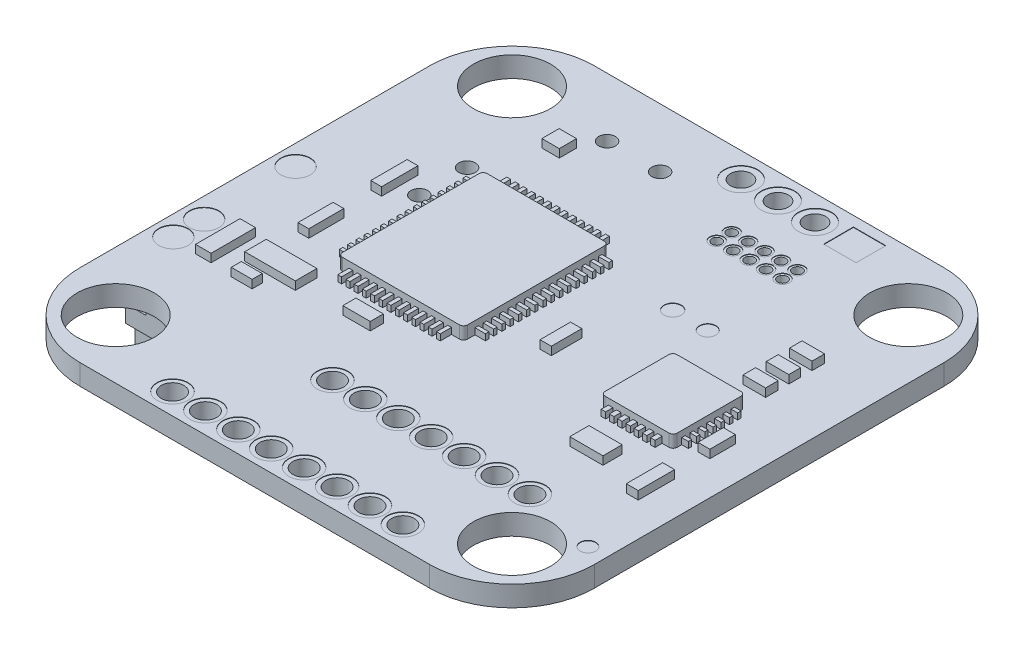
SolidWorks part; units mm, degrees
ref_plane "Front Plane" through (0, 0, 0) normal (0, 0, 1) x (1, 0, 0)
ref_plane "Top Plane" through (0, 0, 0) normal (0, 1, 0) x (1, 0, 0)
ref_plane "Right Plane" through (0, 0, 0) normal (1, 0, 0) x (0, 0, -1)
sketch "Sketch1" plane through (0, 0, 0) normal (0, 1, 0) x (1, 0, 0)
  line L1 (15.875, 15.875) -> (-15.875, 15.875)
  line L2 (15.875, 15.875) -> (15.875, -15.875)
  line L3 (15.875, -15.875) -> (-15.875, -15.875)
  line L4 (-15.875, 15.875) -> (-15.875, -15.875)
  line L5 (15.875, 15.875) -> (-15.875, -15.875) construction
  line L6 (15.875, -15.875) -> (-15.875, 15.875) construction
  point P0 (0, 0)
  dimension "D1" = 31.75
  dimension "D2" = 31.75
extrude "Boss-Extrude1" add sketch "Sketch1" along normal blind 1.27
fillet "Fillet1" radius 5.08 4 edges at (15.875, 0.635, -15.875) (-15.875, 0.635, -15.875) (-15.875, 0.635, 15.875) (15.875, 0.635, 15.875)
sketch "Sketch2" plane through (0, 1.27, 0) normal (0, 1, 0) x (1, 0, 0)
  line L0 (15.875, 0) -> (-15.875, 0) construction
  line L1 (15.875, -10.795) -> (15.875, 10.795) construction
  line L2 (-15.875, 10.795) -> (-15.875, -10.795) construction
  line L3 (0, 0) -> (0, 15.875) construction
  line L4 (10.795, 15.875) -> (-10.795, 15.875) construction
  line L5 (14.3871, 14.3871) -> (0, 0) construction
  arc A0 (15.875, 10.795) -> (10.795, 15.875) centre (10.795, 10.795) ccw construction
  circle A1 centre (12.2354, 12.2354) radius 2.3813
  circle A2 centre (-12.2354, 12.2354) radius 2.3813
  circle A3 centre (-12.2354, -12.2354) radius 2.3813
  circle A4 centre (12.2354, -12.2354) radius 2.3813
  circle A5 centre (-6.3651, 12.2354) radius 0.5132
  circle A6 centre (-3.0883, 12.2354) radius 0.5132
  circle A7 centre (-9.2733, 6.4988) radius 0.5132
  circle A8 centre (-9.2733, 3.5497) radius 0.5132
  dimension "D1" = 4.7625
extrude "Cut-Extrude1" cut sketch "Sketch2" against normal blind 2540
sketch "Sketch3" plane through (0, 1.27, 0) normal (0, 1, 0) x (1, 0, 0)
  line L1 (-0.0888, 6.0397) -> (-7.8229, 6.0397)
  line L2 (-0.0888, 6.0397) -> (-0.0888, -2.9028)
  line L3 (-0.0888, -2.9028) -> (-7.8229, -2.9028)
  line L4 (-7.8229, 6.0397) -> (-7.8229, -2.9028)
  line L5 (-0.0888, 6.0397) -> (-7.8229, -2.9028) construction
  line L6 (-0.0888, -2.9028) -> (-7.8229, 6.0397) construction
  line L7 (12.169, 2.2203) -> (7.7135, 2.2203)
  line L8 (12.169, 2.2203) -> (12.169, -2.2203)
  line L9 (12.169, -2.2203) -> (7.7135, -2.2203)
  line L10 (7.7135, 2.2203) -> (7.7135, -2.2203)
  line L11 (12.169, 2.2203) -> (7.7135, -2.2203) construction
  line L12 (12.169, -2.2203) -> (7.7135, 2.2203) construction
  point P0 (-3.9559, 1.5684)
  point P5 (9.9412, 0)
extrude "Boss-Extrude2" add sketch "Sketch3" along normal blind 0.762
sketch "Sketch4" plane through (0, 1.27, 0) normal (0, 1, 0) x (1, 0, 0)
  line L1 (-10.3847, 4.5784) -> (-11.0506, 4.5784)
  line L2 (-10.3847, 4.5784) -> (-10.3847, 2.3308)
  line L3 (-10.3847, 2.3308) -> (-11.0506, 2.3308)
  line L4 (-11.0506, 4.5784) -> (-11.0506, 2.3308)
  line L5 (-10.3847, 0) -> (-11.0506, 0)
  line L6 (-10.3847, 0) -> (-10.3847, -2.1643)
  line L7 (-10.3847, -2.1643) -> (-11.0506, -2.1643)
  line L8 (-11.0506, 0) -> (-11.0506, -2.1643)
  line L9 (-12.0912, -3.746) -> (-13.0485, -3.746)
  line L10 (-12.0912, -3.746) -> (-12.0912, -6.493)
  line L11 (-12.0912, -6.493) -> (-13.0485, -6.493)
  line L12 (-13.0485, -3.746) -> (-13.0485, -6.493)
  line L13 (-11.1339, -4.0373) -> (-8.0122, -4.0373)
  line L14 (-11.1339, -4.0373) -> (-11.1339, -5.3692)
  line L15 (-11.1339, -5.3692) -> (-8.0122, -5.3692)
  line L16 (-8.0122, -4.0373) -> (-8.0122, -5.3692)
  line L17 (-9.4274, -5.9936) -> (-10.7177, -5.9936)
  line L18 (-9.4274, -5.9936) -> (-9.4274, -6.6179)
  line L19 (-9.4274, -6.6179) -> (-10.7177, -6.6179)
  line L20 (-10.7177, -5.9936) -> (-10.7177, -6.6179)
  line L21 (-5.2236, -4.4119) -> (-3.531, -4.4119)
  line L22 (-5.2236, -4.4119) -> (-5.2236, -5.223)
  line L23 (-5.2236, -5.223) -> (-3.531, -5.223)
  line L24 (-3.531, -4.4119) -> (-3.531, -5.223)
  line L25 (3.3834, 0.9282) -> (2.687, 0.9282)
  line L26 (3.3834, 0.9282) -> (3.3834, -0.9559)
  line L27 (3.3834, -0.9559) -> (2.687, -0.9559)
  line L28 (2.687, 0.9282) -> (2.687, -0.9559)
  line L29 (-6.9386, 10.9225) -> (-8.0122, 10.9225)
  line L30 (-6.9386, 10.9225) -> (-6.9386, 9.8575)
  line L31 (-6.9386, 9.8575) -> (-8.0122, 9.8575)
  line L32 (-8.0122, 10.9225) -> (-8.0122, 9.8575)
  line L33 (12.2307, 7.0722) -> (10.8381, 7.0722)
  line L34 (12.2307, 7.0722) -> (12.2307, 6.294)
  line L35 (12.2307, 6.294) -> (10.8381, 6.294)
  line L36 (10.8381, 7.0722) -> (10.8381, 6.294)
  line L37 (12.2307, 5.5977) -> (10.8381, 5.5977)
  line L38 (12.2307, 5.5977) -> (12.2307, 4.8604)
  line L39 (12.2307, 4.8604) -> (10.8381, 4.8604)
  line L40 (10.8381, 5.5977) -> (10.8381, 4.8604)
  line L41 (12.2307, 4.205) -> (10.8381, 4.205)
  line L42 (12.2307, 4.205) -> (12.2307, 3.4268)
  line L43 (12.2307, 3.4268) -> (10.8381, 3.4268)
  line L44 (10.8381, 4.205) -> (10.8381, 3.4268)
  line L45 (10.8381, -4.0373) -> (8.7901, -4.0373)
  line L46 (10.8381, -4.0373) -> (10.8381, -5.223)
  line L47 (10.8381, -5.223) -> (8.7901, -5.223)
  line L48 (8.7901, -4.0373) -> (8.7901, -5.223)
  line L49 (13.7872, 0) -> (13.0499, 0)
  line L50 (13.7872, 0) -> (13.7872, -1.5703)
  line L51 (13.7872, -1.5703) -> (13.0499, -1.5703)
  line L52 (13.0499, 0) -> (13.0499, -1.5703)
  line L53 (13.7872, -3.746) -> (13.0499, -3.746)
  line L54 (13.7872, -3.746) -> (13.7872, -5.9936)
  line L55 (13.7872, -5.9936) -> (13.0499, -5.9936)
  line L56 (13.0499, -3.746) -> (13.0499, -5.9936)
extrude "Boss-Extrude3" add sketch "Sketch4" along normal blind 0.508
sketch "Sketch5" plane through (0, 1.27, 0) normal (0, 1, 0) x (1, 0, 0)
  line L0 (-0.3573, 5.1281) -> (0.5564, 5.1281)
  line L1 (-0.3573, 5.6361) -> (0.5564, 5.6361)
  line L2 (-0.3573, 5.6361) -> (-0.3573, 5.4223)
  line L3 (-0.3573, 5.4223) -> (0.5564, 5.4223)
  line L4 (0.5564, 5.6361) -> (0.5564, 5.4223)
  line L5 (-7.5497, 5.6361) -> (-8.4633, 5.6361)
  line L6 (-7.5497, 5.6361) -> (-7.5497, 5.4223)
  line L7 (-7.5497, 5.4223) -> (-8.4633, 5.4223)
  line L8 (-8.4633, 5.6361) -> (-8.4633, 5.4223)
  line L9 (-0.3573, 5.1281) -> (-0.3573, 4.9143)
  line L10 (-0.3573, 4.9143) -> (0.5564, 4.9143)
  line L11 (0.5564, 5.1281) -> (0.5564, 4.9143)
  line L12 (-7.5497, 5.1281) -> (-8.4633, 5.1281)
  line L13 (-7.5497, 5.1281) -> (-7.5497, 4.9143)
  line L14 (-7.5497, 4.9143) -> (-8.4633, 4.9143)
  line L15 (-8.4633, 5.1281) -> (-8.4633, 4.9143)
  line L16 (-0.3573, 4.6201) -> (0.5564, 4.6201)
  line L17 (-0.3573, 4.6201) -> (-0.3573, 4.4063)
  line L18 (-0.3573, 4.4063) -> (0.5564, 4.4063)
  line L19 (0.5564, 4.6201) -> (0.5564, 4.4063)
  line L20 (-7.5497, 4.6201) -> (-8.4633, 4.6201)
  line L21 (-7.5497, 4.6201) -> (-7.5497, 4.4063)
  line L22 (-7.5497, 4.4063) -> (-8.4633, 4.4063)
  line L23 (-8.4633, 4.6201) -> (-8.4633, 4.4063)
  line L24 (-0.3573, 4.1121) -> (0.5564, 4.1121)
  line L25 (-0.3573, 4.1121) -> (-0.3573, 3.8983)
  line L26 (-0.3573, 3.8983) -> (0.5564, 3.8983)
  line L27 (0.5564, 4.1121) -> (0.5564, 3.8983)
  line L28 (-7.5497, 4.1121) -> (-8.4633, 4.1121)
  line L29 (-7.5497, 4.1121) -> (-7.5497, 3.8983)
  line L30 (-7.5497, 3.8983) -> (-8.4633, 3.8983)
  line L31 (-8.4633, 4.1121) -> (-8.4633, 3.8983)
  line L32 (-0.3573, 3.6042) -> (0.5564, 3.6042)
  line L33 (-0.3573, 3.6042) -> (-0.3573, 3.3903)
  line L34 (-0.3573, 3.3903) -> (0.5564, 3.3903)
  line L35 (0.5564, 3.6042) -> (0.5564, 3.3903)
  line L36 (-7.5497, 3.6042) -> (-8.4633, 3.6042)
  line L37 (-7.5497, 3.6042) -> (-7.5497, 3.3903)
  line L38 (-7.5497, 3.3903) -> (-8.4633, 3.3903)
  line L39 (-8.4633, 3.6042) -> (-8.4633, 3.3903)
  line L40 (-0.3573, 3.0962) -> (0.5564, 3.0962)
  line L41 (-0.3573, 3.0962) -> (-0.3573, 2.8823)
  line L42 (-0.3573, 2.8823) -> (0.5564, 2.8823)
  line L43 (0.5564, 3.0962) -> (0.5564, 2.8823)
  line L44 (-7.5497, 3.0962) -> (-8.4633, 3.0962)
  line L45 (-7.5497, 3.0962) -> (-7.5497, 2.8823)
  line L46 (-7.5497, 2.8823) -> (-8.4633, 2.8823)
  line L47 (-8.4633, 3.0962) -> (-8.4633, 2.8823)
  line L48 (-0.3573, 2.5882) -> (0.5564, 2.5882)
  line L49 (-0.3573, 2.5882) -> (-0.3573, 2.3743)
  line L50 (-0.3573, 2.3743) -> (0.5564, 2.3743)
  line L51 (0.5564, 2.5882) -> (0.5564, 2.3743)
  line L52 (-7.5497, 2.5882) -> (-8.4633, 2.5882)
  line L53 (-7.5497, 2.5882) -> (-7.5497, 2.3743)
  line L54 (-7.5497, 2.3743) -> (-8.4633, 2.3743)
  line L55 (-8.4633, 2.5882) -> (-8.4633, 2.3743)
  line L56 (-0.3573, 2.0802) -> (0.5564, 2.0802)
  line L57 (-0.3573, 2.0802) -> (-0.3573, 1.8663)
  line L58 (-0.3573, 1.8663) -> (0.5564, 1.8663)
  line L59 (0.5564, 2.0802) -> (0.5564, 1.8663)
  line L60 (-7.5497, 2.0802) -> (-8.4633, 2.0802)
  line L61 (-7.5497, 2.0802) -> (-7.5497, 1.8663)
  line L62 (-7.5497, 1.8663) -> (-8.4633, 1.8663)
  line L63 (-8.4633, 2.0802) -> (-8.4633, 1.8663)
  line L64 (-0.3573, 1.5722) -> (0.5564, 1.5722)
  line L65 (-0.3573, 1.5722) -> (-0.3573, 1.3584)
  line L66 (-0.3573, 1.3584) -> (0.5564, 1.3584)
  line L67 (0.5564, 1.5722) -> (0.5564, 1.3584)
  line L68 (-7.5497, 1.5722) -> (-8.4633, 1.5722)
  line L69 (-7.5497, 1.5722) -> (-7.5497, 1.3584)
  line L70 (-7.5497, 1.3584) -> (-8.4633, 1.3584)
  line L71 (-8.4633, 1.5722) -> (-8.4633, 1.3584)
  line L72 (-0.3573, 1.0642) -> (0.5564, 1.0642)
  line L73 (-0.3573, 1.0642) -> (-0.3573, 0.8504)
  line L74 (-0.3573, 0.8504) -> (0.5564, 0.8504)
  line L75 (0.5564, 1.0642) -> (0.5564, 0.8504)
  line L76 (-7.5497, 1.0642) -> (-8.4633, 1.0642)
  line L77 (-7.5497, 1.0642) -> (-7.5497, 0.8504)
  line L78 (-7.5497, 0.8504) -> (-8.4633, 0.8504)
  line L79 (-8.4633, 1.0642) -> (-8.4633, 0.8504)
  line L80 (-0.3573, 0.5562) -> (0.5564, 0.5562)
  line L81 (-0.3573, 0.5562) -> (-0.3573, 0.3424)
  line L82 (-0.3573, 0.3424) -> (0.5564, 0.3424)
  line L83 (0.5564, 0.5562) -> (0.5564, 0.3424)
  line L84 (-7.5497, 0.5562) -> (-8.4633, 0.5562)
  line L85 (-7.5497, 0.5562) -> (-7.5497, 0.3424)
  line L86 (-7.5497, 0.3424) -> (-8.4633, 0.3424)
  line L87 (-8.4633, 0.5562) -> (-8.4633, 0.3424)
  line L88 (-0.3573, 0.0482) -> (0.5564, 0.0482)
  line L89 (-0.3573, 0.0482) -> (-0.3573, -0.1656)
  line L90 (-0.3573, -0.1656) -> (0.5564, -0.1656)
  line L91 (0.5564, 0.0482) -> (0.5564, -0.1656)
  line L92 (-7.5497, 0.0482) -> (-8.4633, 0.0482)
  line L93 (-7.5497, 0.0482) -> (-7.5497, -0.1656)
  line L94 (-7.5497, -0.1656) -> (-8.4633, -0.1656)
  line L95 (-8.4633, 0.0482) -> (-8.4633, -0.1656)
  line L96 (-0.3573, -0.4598) -> (0.5564, -0.4598)
  line L97 (-0.3573, -0.4598) -> (-0.3573, -0.6736)
  line L98 (-0.3573, -0.6736) -> (0.5564, -0.6736)
  line L99 (0.5564, -0.4598) -> (0.5564, -0.6736)
  line L100 (-7.5497, -0.4598) -> (-8.4633, -0.4598)
  line L101 (-7.5497, -0.4598) -> (-7.5497, -0.6736)
  line L102 (-7.5497, -0.6736) -> (-8.4633, -0.6736)
  line L103 (-8.4633, -0.4598) -> (-8.4633, -0.6736)
  line L104 (-0.3573, -0.9678) -> (0.5564, -0.9678)
  line L105 (-0.3573, -0.9678) -> (-0.3573, -1.1816)
  line L106 (-0.3573, -1.1816) -> (0.5564, -1.1816)
  line L107 (0.5564, -0.9678) -> (0.5564, -1.1816)
  line L108 (-7.5497, -0.9678) -> (-8.4633, -0.9678)
  line L109 (-7.5497, -0.9678) -> (-7.5497, -1.1816)
  line L110 (-7.5497, -1.1816) -> (-8.4633, -1.1816)
  line L111 (-8.4633, -0.9678) -> (-8.4633, -1.1816)
  line L112 (-0.3573, -1.4758) -> (0.5564, -1.4758)
  line L113 (-0.3573, -1.4758) -> (-0.3573, -1.6896)
  line L114 (-0.3573, -1.6896) -> (0.5564, -1.6896)
  line L115 (0.5564, -1.4758) -> (0.5564, -1.6896)
  line L116 (-7.5497, -1.4758) -> (-8.4633, -1.4758)
  line L117 (-7.5497, -1.4758) -> (-7.5497, -1.6896)
  line L118 (-7.5497, -1.6896) -> (-8.4633, -1.6896)
  line L119 (-8.4633, -1.4758) -> (-8.4633, -1.6896)
  line L120 (-0.3573, -1.9838) -> (0.5564, -1.9838)
  line L121 (-0.3573, -1.9838) -> (-0.3573, -2.1976)
  line L122 (-0.3573, -2.1976) -> (0.5564, -2.1976)
  line L123 (0.5564, -1.9838) -> (0.5564, -2.1976)
  line L124 (-7.5497, -1.9838) -> (-8.4633, -1.9838)
  line L125 (-7.5497, -1.9838) -> (-7.5497, -2.1976)
  line L126 (-7.5497, -2.1976) -> (-8.4633, -2.1976)
  line L127 (-8.4633, -1.9838) -> (-8.4633, -2.1976)
  line L128 (-6.6529, 5.7722) -> (-6.4196, 5.7722)
  line L129 (-7.1609, 5.7722) -> (-6.9276, 5.7722)
  line L130 (-7.1609, 5.7722) -> (-7.1609, 6.8413)
  line L131 (-7.1609, 6.8413) -> (-6.9276, 6.8413)
  line L132 (-6.9276, 5.7722) -> (-6.9276, 6.8413)
  line L133 (-7.1609, -2.5088) -> (-6.9276, -2.5088)
  line L134 (-7.1609, -2.5088) -> (-7.1609, -3.5974)
  line L135 (-7.1609, -3.5974) -> (-6.9276, -3.5974)
  line L136 (-6.9276, -2.5088) -> (-6.9276, -3.5974)
  line L137 (-6.6529, 5.7722) -> (-6.6529, 6.8413)
  line L138 (-6.6529, 6.8413) -> (-6.4196, 6.8413)
  line L139 (-6.4196, 5.7722) -> (-6.4196, 6.8413)
  line L140 (-6.6529, -2.5088) -> (-6.4196, -2.5088)
  line L141 (-6.6529, -2.5088) -> (-6.6529, -3.5974)
  line L142 (-6.6529, -3.5974) -> (-6.4196, -3.5974)
  line L143 (-6.4196, -2.5088) -> (-6.4196, -3.5974)
  line L144 (-6.1449, 5.7722) -> (-5.9116, 5.7722)
  line L145 (-6.1449, 5.7722) -> (-6.1449, 6.8413)
  line L146 (-6.1449, 6.8413) -> (-5.9116, 6.8413)
  line L147 (-5.9116, 5.7722) -> (-5.9116, 6.8413)
  line L148 (-6.1449, -2.5088) -> (-5.9116, -2.5088)
  line L149 (-6.1449, -2.5088) -> (-6.1449, -3.5974)
  line L150 (-6.1449, -3.5974) -> (-5.9116, -3.5974)
  line L151 (-5.9116, -2.5088) -> (-5.9116, -3.5974)
  line L152 (-5.6369, 5.7722) -> (-5.4036, 5.7722)
  line L153 (-5.6369, 5.7722) -> (-5.6369, 6.8413)
  line L154 (-5.6369, 6.8413) -> (-5.4036, 6.8413)
  line L155 (-5.4036, 5.7722) -> (-5.4036, 6.8413)
  line L156 (-5.6369, -2.5088) -> (-5.4036, -2.5088)
  line L157 (-5.6369, -2.5088) -> (-5.6369, -3.5974)
  line L158 (-5.6369, -3.5974) -> (-5.4036, -3.5974)
  line L159 (-5.4036, -2.5088) -> (-5.4036, -3.5974)
  line L160 (-5.1289, 5.7722) -> (-4.8956, 5.7722)
  line L161 (-5.1289, 5.7722) -> (-5.1289, 6.8413)
  line L162 (-5.1289, 6.8413) -> (-4.8956, 6.8413)
  line L163 (-4.8956, 5.7722) -> (-4.8956, 6.8413)
  line L164 (-5.1289, -2.5088) -> (-4.8956, -2.5088)
  line L165 (-5.1289, -2.5088) -> (-5.1289, -3.5974)
  line L166 (-5.1289, -3.5974) -> (-4.8956, -3.5974)
  line L167 (-4.8956, -2.5088) -> (-4.8956, -3.5974)
  line L168 (-4.6209, 5.7722) -> (-4.3876, 5.7722)
  line L169 (-4.6209, 5.7722) -> (-4.6209, 6.8413)
  line L170 (-4.6209, 6.8413) -> (-4.3876, 6.8413)
  line L171 (-4.3876, 5.7722) -> (-4.3876, 6.8413)
  line L172 (-4.6209, -2.5088) -> (-4.3876, -2.5088)
  line L173 (-4.6209, -2.5088) -> (-4.6209, -3.5974)
  line L174 (-4.6209, -3.5974) -> (-4.3876, -3.5974)
  line L175 (-4.3876, -2.5088) -> (-4.3876, -3.5974)
  line L176 (-4.1129, 5.7722) -> (-3.8796, 5.7722)
  line L177 (-4.1129, 5.7722) -> (-4.1129, 6.8413)
  line L178 (-4.1129, 6.8413) -> (-3.8796, 6.8413)
  line L179 (-3.8796, 5.7722) -> (-3.8796, 6.8413)
  line L180 (-4.1129, -2.5088) -> (-3.8796, -2.5088)
  line L181 (-4.1129, -2.5088) -> (-4.1129, -3.5974)
  line L182 (-4.1129, -3.5974) -> (-3.8796, -3.5974)
  line L183 (-3.8796, -2.5088) -> (-3.8796, -3.5974)
  line L184 (-3.6049, 5.7722) -> (-3.3716, 5.7722)
  line L185 (-3.6049, 5.7722) -> (-3.6049, 6.8413)
  line L186 (-3.6049, 6.8413) -> (-3.3716, 6.8413)
  line L187 (-3.3716, 5.7722) -> (-3.3716, 6.8413)
  line L188 (-3.6049, -2.5088) -> (-3.3716, -2.5088)
  line L189 (-3.6049, -2.5088) -> (-3.6049, -3.5974)
  line L190 (-3.6049, -3.5974) -> (-3.3716, -3.5974)
  line L191 (-3.3716, -2.5088) -> (-3.3716, -3.5974)
  line L192 (-3.0969, 5.7722) -> (-2.8636, 5.7722)
  line L193 (-3.0969, 5.7722) -> (-3.0969, 6.8413)
  line L194 (-3.0969, 6.8413) -> (-2.8636, 6.8413)
  line L195 (-2.8636, 5.7722) -> (-2.8636, 6.8413)
  line L196 (-3.0969, -2.5088) -> (-2.8636, -2.5088)
  line L197 (-3.0969, -2.5088) -> (-3.0969, -3.5974)
  line L198 (-3.0969, -3.5974) -> (-2.8636, -3.5974)
  line L199 (-2.8636, -2.5088) -> (-2.8636, -3.5974)
  line L200 (-2.5889, 5.7722) -> (-2.3556, 5.7722)
  line L201 (-2.5889, 5.7722) -> (-2.5889, 6.8413)
  line L202 (-2.5889, 6.8413) -> (-2.3556, 6.8413)
  line L203 (-2.3556, 5.7722) -> (-2.3556, 6.8413)
  line L204 (-2.5889, -2.5088) -> (-2.3556, -2.5088)
  line L205 (-2.5889, -2.5088) -> (-2.5889, -3.5974)
  line L206 (-2.5889, -3.5974) -> (-2.3556, -3.5974)
  line L207 (-2.3556, -2.5088) -> (-2.3556, -3.5974)
  line L208 (-2.0809, 5.7722) -> (-1.8476, 5.7722)
  line L209 (-2.0809, 5.7722) -> (-2.0809, 6.8413)
  line L210 (-2.0809, 6.8413) -> (-1.8476, 6.8413)
  line L211 (-1.8476, 5.7722) -> (-1.8476, 6.8413)
  line L212 (-2.0809, -2.5088) -> (-1.8476, -2.5088)
  line L213 (-2.0809, -2.5088) -> (-2.0809, -3.5974)
  line L214 (-2.0809, -3.5974) -> (-1.8476, -3.5974)
  line L215 (-1.8476, -2.5088) -> (-1.8476, -3.5974)
  line L216 (-1.5729, 5.7722) -> (-1.3396, 5.7722)
  line L217 (-1.5729, 5.7722) -> (-1.5729, 6.8413)
  line L218 (-1.5729, 6.8413) -> (-1.3396, 6.8413)
  line L219 (-1.3396, 5.7722) -> (-1.3396, 6.8413)
  line L220 (-1.5729, -2.5088) -> (-1.3396, -2.5088)
  line L221 (-1.5729, -2.5088) -> (-1.5729, -3.5974)
  line L222 (-1.5729, -3.5974) -> (-1.3396, -3.5974)
  line L223 (-1.3396, -2.5088) -> (-1.3396, -3.5974)
  line L224 (-1.0649, 5.7722) -> (-0.8316, 5.7722)
  line L225 (-1.0649, 5.7722) -> (-1.0649, 6.8413)
  line L226 (-1.0649, 6.8413) -> (-0.8316, 6.8413)
  line L227 (-0.8316, 5.7722) -> (-0.8316, 6.8413)
  line L228 (-1.0649, -2.5088) -> (-0.8316, -2.5088)
  line L229 (-1.0649, -2.5088) -> (-1.0649, -3.5974)
  line L230 (-1.0649, -3.5974) -> (-0.8316, -3.5974)
  line L231 (-0.8316, -2.5088) -> (-0.8316, -3.5974)
  line L232 (7.3458, -1.1816) -> (8.1656, -1.1816)
  line L233 (7.3458, -1.6896) -> (8.1656, -1.6896)
  line L234 (7.3458, -1.6896) -> (7.3458, -1.4758)
  line L235 (7.3458, -1.4758) -> (8.1656, -1.4758)
  line L236 (8.1656, -1.6896) -> (8.1656, -1.4758)
  line L237 (11.8217, -1.6896) -> (12.5758, -1.6896)
  line L238 (11.8217, -1.6896) -> (11.8217, -1.4794)
  line L239 (11.8217, -1.4794) -> (12.5758, -1.4794)
  line L240 (12.5758, -1.6896) -> (12.5758, -1.4794)
  line L241 (7.3458, -1.1816) -> (7.3458, -0.9678)
  line L242 (7.3458, -0.9678) -> (8.1656, -0.9678)
  line L243 (8.1656, -1.1816) -> (8.1656, -0.9678)
  line L244 (11.8217, -1.1816) -> (12.5758, -1.1816)
  line L245 (11.8217, -1.1816) -> (11.8217, -0.9714)
  line L246 (11.8217, -0.9714) -> (12.5758, -0.9714)
  line L247 (12.5758, -1.1816) -> (12.5758, -0.9714)
  line L248 (7.3458, -0.6736) -> (8.1656, -0.6736)
  line L249 (7.3458, -0.6736) -> (7.3458, -0.4598)
  line L250 (7.3458, -0.4598) -> (8.1656, -0.4598)
  line L251 (8.1656, -0.6736) -> (8.1656, -0.4598)
  line L252 (11.8217, -0.6736) -> (12.5758, -0.6736)
  line L253 (11.8217, -0.6736) -> (11.8217, -0.4634)
  line L254 (11.8217, -0.4634) -> (12.5758, -0.4634)
  line L255 (12.5758, -0.6736) -> (12.5758, -0.4634)
  line L256 (7.3458, -0.1656) -> (8.1656, -0.1656)
  line L257 (7.3458, -0.1656) -> (7.3458, 0.0482)
  line L258 (7.3458, 0.0482) -> (8.1656, 0.0482)
  line L259 (8.1656, -0.1656) -> (8.1656, 0.0482)
  line L260 (11.8217, -0.1656) -> (12.5758, -0.1656)
  line L261 (11.8217, -0.1656) -> (11.8217, 0.0446)
  line L262 (11.8217, 0.0446) -> (12.5758, 0.0446)
  line L263 (12.5758, -0.1656) -> (12.5758, 0.0446)
  line L264 (7.3458, 0.3424) -> (8.1656, 0.3424)
  line L265 (7.3458, 0.3424) -> (7.3458, 0.5562)
  line L266 (7.3458, 0.5562) -> (8.1656, 0.5562)
  line L267 (8.1656, 0.3424) -> (8.1656, 0.5562)
  line L268 (11.8217, 0.3424) -> (12.5758, 0.3424)
  line L269 (11.8217, 0.3424) -> (11.8217, 0.5526)
  line L270 (11.8217, 0.5526) -> (12.5758, 0.5526)
  line L271 (12.5758, 0.3424) -> (12.5758, 0.5526)
  line L272 (7.3458, 0.8504) -> (8.1656, 0.8504)
  line L273 (7.3458, 0.8504) -> (7.3458, 1.0642)
  line L274 (7.3458, 1.0642) -> (8.1656, 1.0642)
  line L275 (8.1656, 0.8504) -> (8.1656, 1.0642)
  line L276 (11.8217, 0.8504) -> (12.5758, 0.8504)
  line L277 (11.8217, 0.8504) -> (11.8217, 1.0606)
  line L278 (11.8217, 1.0606) -> (12.5758, 1.0606)
  line L279 (12.5758, 0.8504) -> (12.5758, 1.0606)
  line L280 (7.3458, 1.3584) -> (8.1656, 1.3584)
  line L281 (7.3458, 1.3584) -> (7.3458, 1.5722)
  line L282 (7.3458, 1.5722) -> (8.1656, 1.5722)
  line L283 (8.1656, 1.3584) -> (8.1656, 1.5722)
  line L284 (11.8217, 1.3584) -> (12.5758, 1.3584)
  line L285 (11.8217, 1.3584) -> (11.8217, 1.5686)
  line L286 (11.8217, 1.5686) -> (12.5758, 1.5686)
  line L287 (12.5758, 1.3584) -> (12.5758, 1.5686)
  line L288 (8.6736, -1.9838) -> (8.9523, -1.9838)
  line L289 (8.1656, 1.8663) -> (8.4443, 1.8663)
  line L290 (8.1656, 1.8663) -> (8.1656, 2.5882)
  line L291 (8.1656, 2.5882) -> (8.4443, 2.5882)
  line L292 (8.4443, 1.8663) -> (8.4443, 2.5882)
  line L293 (8.1656, -1.9838) -> (8.4443, -1.9838)
  line L294 (8.1656, -1.9838) -> (8.1656, -2.6599)
  line L295 (8.1656, -2.6599) -> (8.4443, -2.6599)
  line L296 (8.4443, -1.9838) -> (8.4443, -2.6599)
  line L297 (8.6736, -1.9838) -> (8.6736, -2.6599)
  line L298 (8.6736, -2.6599) -> (8.9523, -2.6599)
  line L299 (8.9523, -1.9838) -> (8.9523, -2.6599)
  line L300 (8.6736, 1.8663) -> (8.9523, 1.8663)
  line L301 (8.6736, 1.8663) -> (8.6736, 2.5882)
  line L302 (8.6736, 2.5882) -> (8.9523, 2.5882)
  line L303 (8.9523, 1.8663) -> (8.9523, 2.5882)
  line L304 (9.1816, -1.9838) -> (9.4603, -1.9838)
  line L305 (9.1816, -1.9838) -> (9.1816, -2.6599)
  line L306 (9.1816, -2.6599) -> (9.4603, -2.6599)
  line L307 (9.4603, -1.9838) -> (9.4603, -2.6599)
  line L308 (9.1816, 1.8663) -> (9.4603, 1.8663)
  line L309 (9.1816, 1.8663) -> (9.1816, 2.5882)
  line L310 (9.1816, 2.5882) -> (9.4603, 2.5882)
  line L311 (9.4603, 1.8663) -> (9.4603, 2.5882)
  line L312 (9.6896, -1.9838) -> (9.9683, -1.9838)
  line L313 (9.6896, -1.9838) -> (9.6896, -2.6599)
  line L314 (9.6896, -2.6599) -> (9.9683, -2.6599)
  line L315 (9.9683, -1.9838) -> (9.9683, -2.6599)
  line L316 (9.6896, 1.8663) -> (9.9683, 1.8663)
  line L317 (9.6896, 1.8663) -> (9.6896, 2.5882)
  line L318 (9.6896, 2.5882) -> (9.9683, 2.5882)
  line L319 (9.9683, 1.8663) -> (9.9683, 2.5882)
  line L320 (10.1976, -1.9838) -> (10.4763, -1.9838)
  line L321 (10.1976, -1.9838) -> (10.1976, -2.6599)
  line L322 (10.1976, -2.6599) -> (10.4763, -2.6599)
  line L323 (10.4763, -1.9838) -> (10.4763, -2.6599)
  line L324 (10.1976, 1.8663) -> (10.4763, 1.8663)
  line L325 (10.1976, 1.8663) -> (10.1976, 2.5882)
  line L326 (10.1976, 2.5882) -> (10.4763, 2.5882)
  line L327 (10.4763, 1.8663) -> (10.4763, 2.5882)
  line L328 (10.7056, -1.9838) -> (10.9843, -1.9838)
  line L329 (10.7056, -1.9838) -> (10.7056, -2.6599)
  line L330 (10.7056, -2.6599) -> (10.9843, -2.6599)
  line L331 (10.9843, -1.9838) -> (10.9843, -2.6599)
  line L332 (10.7056, 1.8663) -> (10.9843, 1.8663)
  line L333 (10.7056, 1.8663) -> (10.7056, 2.5882)
  line L334 (10.7056, 2.5882) -> (10.9843, 2.5882)
  line L335 (10.9843, 1.8663) -> (10.9843, 2.5882)
  line L336 (11.2136, -1.9838) -> (11.4923, -1.9838)
  line L337 (11.2136, -1.9838) -> (11.2136, -2.6599)
  line L338 (11.2136, -2.6599) -> (11.4923, -2.6599)
  line L339 (11.4923, -1.9838) -> (11.4923, -2.6599)
  line L340 (11.2136, 1.8663) -> (11.4923, 1.8663)
  line L341 (11.2136, 1.8663) -> (11.2136, 2.5882)
  line L342 (11.2136, 2.5882) -> (11.4923, 2.5882)
  line L343 (11.4923, 1.8663) -> (11.4923, 2.5882)
  dimension "D1" = 16
  dimension "D2" = 13
  dimension "D3" = 7
  dimension "D4" = 7
extrude "Boss-Extrude4" add sketch "Sketch5" along normal blind 0.381
sketch "Sketch6" plane through (0, 1.27, 0) normal (0, 1, 0) x (1, 0, 0)
  line L1 (7.8249, 13.4231) -> (5.8271, 13.4231)
  line L2 (7.8249, 13.4231) -> (7.8249, 15.2545)
  line L3 (7.8249, 15.2545) -> (5.8271, 15.2545)
  line L4 (5.8271, 13.4231) -> (5.8271, 15.2545)
  circle A0 centre (4.3703, 14.3388) radius 1.028
  circle A1 centre (2.0843, 14.3388) radius 1.028
  circle A2 centre (-0.2017, 14.3388) radius 1.028
  circle A3 centre (6.4098, 11.2171) radius 0.4263
  circle A4 centre (6.4098, 10.2934) radius 0.4263
  circle A5 centre (5.3938, 11.2171) radius 0.4263
  circle A6 centre (5.3938, 10.2934) radius 0.4263
  circle A7 centre (4.3778, 11.2171) radius 0.4263
  circle A8 centre (4.3778, 10.2934) radius 0.4263
  circle A9 centre (3.3618, 11.2171) radius 0.4263
  circle A10 centre (3.3618, 10.2934) radius 0.4263
  circle A11 centre (2.3458, 11.2171) radius 0.4263
  circle A12 centre (2.3458, 10.2934) radius 0.4263
  circle A13 centre (-14.6347, 1.2695) radius 0.9051
  circle A14 centre (-14.6347, -4.3754) radius 0.9051
  circle A15 centre (-14.6347, -6.2731) radius 0.9051
  circle A16 centre (6.8557, 5.2299) radius 0.5046
  circle A17 centre (4.6914, 5.2299) radius 0.5345
  circle A18 centre (14.7259, -10.0382) radius 0.4787
  circle A19 centre (10.1218, -9.0151) radius 0.9522
  circle A20 centre (8.0898, -9.0151) radius 0.9522
  circle A21 centre (6.0578, -9.0151) radius 0.9522
  circle A22 centre (4.0258, -9.0151) radius 0.9522
  circle A23 centre (1.9938, -9.0151) radius 0.9522
  circle A24 centre (-0.0382, -9.0151) radius 0.9522
  circle A25 centre (-2.0702, -9.0151) radius 0.9522
  circle A26 centre (7.8249, -14.5636) radius 0.9522
  circle A27 centre (5.7929, -14.5636) radius 0.9522
  circle A28 centre (3.7609, -14.5636) radius 0.9522
  circle A29 centre (1.7289, -14.5636) radius 0.9522
  circle A30 centre (-0.3031, -14.5636) radius 0.9522
  circle A31 centre (-2.3351, -14.5636) radius 0.9522
  circle A32 centre (-4.3671, -14.5636) radius 0.9522
  circle A33 centre (-6.3991, -14.5636) radius 0.9522
  dimension "D1" = 3
  dimension "D2" = 5
  dimension "D3" = 7
  dimension "D4" = 8
extrude "Cut-Extrude2" cut sketch "Sketch6" against normal blind 0.0254
fillet "Fillet2" radius 0.254 8 edges at (-0.0888, 1.651, 2.9028) (-7.8229, 1.651, 2.9028) (-7.8229, 1.651, -6.0397) (-0.0888, 1.651, -6.0397) (12.169, 1.651, 2.2203) (12.169, 1.651, -2.2203) (7.7135, 1.651, 2.2203) (7.7135, 1.651, -2.2203)
sketch "Sketch7" plane through (0, 0, 0) normal (0, -1, 0) x (1, 0, 0)
  line L1 (12.5906, 7.0757) -> (-2.1435, 7.0757)
  line L2 (12.5906, 7.0757) -> (12.5906, -8.7822)
  line L3 (12.5906, -8.7822) -> (-2.1435, -8.7822)
  line L4 (-2.1435, 7.0757) -> (-2.1435, -8.7822)
  line L5 (-10.8009, -1.4151) -> (-15.379, -1.4151)
  line L6 (-10.8009, -1.4151) -> (-10.8009, -8.7822)
  line L7 (-10.8009, -8.7822) -> (-15.379, -8.7822)
  line L8 (-15.379, -1.4151) -> (-15.379, -8.7822)
extrude "Boss-Extrude5" add sketch "Sketch7" along normal blind 1.905
sketch "Sketch8" plane through (12.5906, 0, 0) normal (1, 0, 0) x (0, 0, -1)
  line L1 (-6.6081, -0.2398) -> (8.2748, -0.2398)
  line L2 (-6.6081, -0.2398) -> (-6.6081, -1.6198)
  line L3 (-6.6081, -1.6198) -> (8.2748, -1.6198)
  line L4 (8.2748, -0.2398) -> (8.2748, -1.6198)
extrude "Cut-Extrude3" cut sketch "Sketch8" against normal blind 13.97
sketch "Sketch10" plane through (-15.379, 0, 0) normal (-1, 0, 0) x (0, 0, 1)
  line L1 (-1.6982, -1.5672) -> (-8.497, -1.5672)
  line L2 (-1.6982, -1.5672) -> (-1.6982, -0.2327)
  line L3 (-1.6982, -0.2327) -> (-8.497, -0.2327)
  line L4 (-8.497, -1.5672) -> (-8.497, -0.2327)
extrude "Cut-Extrude4" cut sketch "Sketch10" against normal blind 3.81
sketch "Sketch11" plane through (0, -1.905, 0) normal (0, -1, 0) x (1, 0, 0)
  line L0 (12.5906, 3.9734) -> (7.7579, 1.1034)
  line L1 (12.5906, -8.7822) -> (12.5906, 7.0757) construction
  line L2 (7.7579, 1.1034) -> (7.7579, -5.7178)
  line L3 (7.7579, -5.7178) -> (12.5906, -7.6037)
  line L4 (12.5906, -7.6037) -> (12.5906, 3.9734)
extrude "Cut-Extrude5" cut sketch "Sketch11" against normal blind 1.27
sketch "Sketch12" plane through (0, -0.2398, 0) normal (0, -1, 0) x (1, 0, 0)
  line L1 (6.4722, 0.5411) -> (3.4338, 0.5411)
  line L2 (6.4722, 0.5411) -> (6.4722, -3.2881)
  line L3 (6.4722, -3.2881) -> (3.4338, -3.2881)
  line L4 (3.4338, 0.5411) -> (3.4338, -3.2881)
  line L5 (6.4722, -3.8292) -> (3.4338, -3.8292)
  line L6 (6.4722, -3.8292) -> (6.4722, -7.8249)
  line L7 (6.4722, -7.8249) -> (3.4338, -7.8249)
  line L8 (3.4338, -3.8292) -> (3.4338, -7.8249)
extrude "Cut-Extrude6" cut sketch "Sketch12" against normal blind 1.27
sketch "Sketch13" plane through (0, -0.2398, 0) normal (0, -1, 0) x (1, 0, 0)
  line L0 (12.5906, -8.2748) -> (12.5906, 6.6081) construction
  line L1 (12.5906, 1.9979) -> (10.9258, 1.9979)
  line L2 (12.5906, 1.9979) -> (12.5906, -7.6584)
  line L3 (12.5906, -7.6584) -> (10.9258, -7.6584)
  line L4 (10.9258, 1.9979) -> (10.9258, -7.6584)
extrude "Cut-Extrude7" cut sketch "Sketch13" against normal up to surface (0.2398 mm away) up to face at (-12.2354, 0, -14.6166)
sketch "Sketch14" plane through (0, -1.905, 0) normal (0, -1, 0) x (1, 0, 0)
  line L0 (-10.8009, -8.7822) -> (-10.8009, -1.4151) construction
  line L1 (-10.8009, -2.7054) -> (-12.2161, -2.7054)
  line L2 (-10.8009, -2.7054) -> (-10.8009, -4.1622)
  line L3 (-10.8009, -4.1622) -> (-12.2161, -4.1622)
  line L4 (-12.2161, -2.7054) -> (-12.2161, -4.1622)
  line L6 (-10.8009, -6.2017) -> (-12.2161, -6.2017)
  line L7 (-10.8009, -6.2017) -> (-10.8009, -7.8249)
  line L8 (-10.8009, -7.8249) -> (-12.2161, -7.8249)
  line L9 (-12.2161, -6.2017) -> (-12.2161, -7.8249)
  line L10 (-13.3398, -2.2892) -> (-14.8799, -2.2892)
  line L11 (-13.3398, -2.2892) -> (-13.3398, -3.1216)
  line L12 (-13.3398, -3.1216) -> (-14.8799, -3.1216)
  line L13 (-14.8799, -2.2892) -> (-14.8799, -3.1216)
  line L14 (-13.3398, -7.1174) -> (-14.8799, -7.1174)
  line L15 (-13.3398, -7.1174) -> (-13.3398, -8.1163)
  line L16 (-13.3398, -8.1163) -> (-14.8799, -8.1163)
  line L17 (-14.8799, -7.1174) -> (-14.8799, -8.1163)
extrude "Cut-Extrude8" cut sketch "Sketch14" against normal blind 1.27
sketch "Sketch15" plane through (0, 0, 0) normal (0, -1, 0) x (-1, 0, 0)
  line L0 (9.3025, -1.7065) -> (9.3025, -0.9646)
  line L1 (15.4612, -8.4144) -> (9.3025, -8.4144)
  line L2 (15.4612, -8.4144) -> (15.4612, -0.9646)
  line L3 (15.4612, -0.9646) -> (9.3025, -0.9646)
  line L4 (9.3025, -8.4144) -> (9.3025, -7.7001)
  line L5 (9.3025, -7.7001) -> (10.8841, -7.7001)
  line L7 (9.3025, -1.7065) -> (10.8841, -1.7065)
  line L8 (10.8841, -7.7001) -> (10.8841, -1.7065)
extrude "Boss-Extrude6" add sketch "Sketch15" along normal blind 4.572
sketch "Sketch16" plane through (-15.4612, 0, 0) normal (-1, 0, 0) x (0, 0, 1)
  line L0 (5.235, -3.8269) -> (7.4617, -3.8269)
  line L1 (1.9941, -0.868) -> (7.4617, -0.868)
  line L2 (1.9941, -0.868) -> (1.9941, -3.8269)
  line L3 (1.9941, -3.8269) -> (4.1499, -3.8269)
  line L4 (7.4617, -0.868) -> (7.4617, -3.8269)
  line L6 (4.1499, -3.8269) -> (4.1499, -4.2647)
  line L7 (4.1499, -4.2647) -> (5.235, -4.2647)
  line L8 (5.235, -3.8269) -> (5.235, -4.2647)
  line L9 (2.9362, -2.6832) -> (3.6166, -2.6832)
  line L10 (2.9362, -2.6832) -> (2.9362, -3.1245)
  line L11 (2.9362, -3.1245) -> (3.6166, -3.1245)
  line L12 (3.6166, -2.6832) -> (3.6166, -3.1245)
  line L13 (5.8786, -2.6832) -> (6.5223, -2.6832)
  line L14 (5.8786, -2.6832) -> (5.8786, -3.1245)
  line L15 (5.8786, -3.1245) -> (6.5223, -3.1245)
  line L16 (6.5223, -2.6832) -> (6.5223, -3.1245)
  line L17 (0.9646, -4.572) -> (0.9646, 0) construction
  line L18 (0.9646, -2.6832) -> (1.5202, -2.6832)
  line L19 (0.9646, -2.6832) -> (0.9646, -3.1245)
  line L20 (0.9646, -3.1245) -> (1.5202, -3.1245)
  line L21 (1.5202, -2.6832) -> (1.5202, -3.1245)
  line L22 (8.4144, -4.572) -> (8.4144, 0) construction
  line L23 (8.4144, -3.1245) -> (7.8096, -3.1245)
  line L24 (8.4144, -3.1245) -> (8.4144, -2.6832)
  line L25 (8.4144, -2.6832) -> (7.8096, -2.6832)
  line L26 (7.8096, -3.1245) -> (7.8096, -2.6832)
extrude "Cut-Extrude9" cut sketch "Sketch16" against normal blind 4.572
sketch "Sketch17" plane through (-15.4612, 0, 0) normal (-1, 0, 0) x (0, 0, 1)
  line L0 (8.4144, -4.572) -> (8.4144, -3.1245) construction
  line L1 (0.9646, -3.1245) -> (1.5202, -3.1245)
  line L2 (0.9646, -3.1245) -> (0.9646, -3.8594)
  line L3 (0.9646, -3.8594) -> (1.5202, -3.8594)
  line L4 (1.5202, -3.1245) -> (1.5202, -3.8594)
  line L5 (7.8096, -3.1245) -> (8.4144, -3.1245)
  line L6 (7.8096, -3.1245) -> (7.8096, -3.8594)
  line L7 (7.8096, -3.8594) -> (8.4144, -3.8594)
  line L8 (8.4144, -3.1245) -> (8.4144, -3.8594)
extrude "Cut-Extrude10" cut sketch "Sketch17" against normal blind 3.048
sketch "Sketch18" plane through (-15.4612, 0, 0) normal (-1, 0, 0) x (0, 0, 1)
  line L0 (8.4144, -4.572) -> (0.9646, -4.572) construction
  line L1 (0.9646, -3.8594) -> (1.5202, -3.8594)
  line L2 (0.9646, -3.8594) -> (0.9646, -4.572)
  line L3 (0.9646, -4.572) -> (1.5202, -4.572)
  line L4 (1.5202, -3.8594) -> (1.5202, -4.572)
  line L5 (0.9646, -2.6832) -> (0.9646, 0) construction
  line L6 (7.8096, -3.8594) -> (8.4144, -3.8594)
  line L7 (7.8096, -3.8594) -> (7.8096, -4.572)
  line L8 (7.8096, -4.572) -> (8.4144, -4.572)
  line L9 (8.4144, -3.8594) -> (8.4144, -4.572)
  line L10 (0.9646, -1.6286) -> (1.5202, -1.6286)
  line L11 (0.9646, -1.6286) -> (0.9646, 0)
  line L12 (0.9646, 0) -> (1.5202, 0)
  line L13 (1.5202, -1.6286) -> (1.5202, 0)
  line L14 (8.4144, 0) -> (0.9646, 0) construction
  line L15 (8.4144, -2.6832) -> (8.4144, 0) construction
  line L16 (8.4144, -1.6286) -> (7.8096, -1.6286)
  line L17 (8.4144, -1.6286) -> (8.4144, 0)
  line L18 (8.4144, 0) -> (7.8096, 0)
  line L19 (7.8096, -1.6286) -> (7.8096, 0)
extrude "Cut-Extrude11" cut sketch "Sketch18" against normal blind 1.27
sketch "Sketch19" plane through (0, 0, 0) normal (0, -1, 0) x (-1, 0, 0)
  line L1 (7.7209, 13.4439) -> (1.5608, 13.4439)
  line L2 (7.7209, 13.4439) -> (7.7209, 10.6552)
  line L3 (7.7209, 10.6552) -> (1.5608, 10.6552)
  line L4 (1.5608, 13.4439) -> (1.5608, 10.6552)
extrude "Boss-Extrude7" add sketch "Sketch19" along normal blind 1.27
sketch "Sketch20" plane through (0, 0, 0) normal (0, -1, 0) x (-1, 0, 0)
  line L0 (10.8841, -1.7065) -> (10.8841, -7.7001) construction
  line L1 (8.0539, 6.6595) -> (5.9728, 6.6595)
  line L2 (8.0539, 6.6595) -> (8.0539, 5.4525)
  line L3 (8.0539, 5.4525) -> (5.9728, 5.4525)
  line L4 (5.9728, 6.6595) -> (5.9728, 5.4525)
  line L5 (6.5971, 3.3298) -> (3.7668, 3.3298)
  line L6 (6.5971, 3.3298) -> (6.5971, 1.6649)
  line L7 (6.5971, 1.6649) -> (3.7668, 1.6649)
  line L8 (3.7668, 3.3298) -> (3.7668, 1.6649)
  line L9 (4.8906, 7.9082) -> (4.2663, 7.9082)
  line L10 (4.8906, 7.9082) -> (4.8906, 6.056)
  line L11 (4.8906, 6.056) -> (4.2663, 6.056)
  line L12 (4.2663, 7.9082) -> (4.2663, 6.056)
  line L13 (3.7668, 7.9082) -> (3.1008, 7.9082)
  line L14 (3.7668, 7.9082) -> (3.7668, 6.056)
  line L15 (3.7668, 6.056) -> (3.1008, 6.056)
  line L16 (3.1008, 7.9082) -> (3.1008, 6.056)
  line L17 (4.2663, 9.6563) -> (3.1008, 9.6563)
  line L18 (4.2663, 9.6563) -> (4.2663, 8.8655)
  line L19 (4.2663, 8.8655) -> (3.1008, 8.8655)
  line L20 (3.1008, 9.6563) -> (3.1008, 8.8655)
  line L21 (10.1766, 0.4578) -> (9.053, 0.4578)
  line L22 (10.1766, 0.4578) -> (10.1766, -0.1953)
  line L23 (10.1766, -0.1953) -> (9.053, -0.1953)
  line L24 (9.053, 0.4578) -> (9.053, -0.1953)
  line L25 (10.8841, -3.4379) -> (8.0539, -3.4379)
  line L26 (10.8841, -3.4379) -> (10.8841, -4.2374)
  line L27 (10.8841, -4.2374) -> (8.0539, -4.2374)
  line L28 (8.0539, -3.4379) -> (8.0539, -4.2374)
  line L30 (10.8841, -5.1074) -> (8.0539, -5.1074)
  line L31 (10.8841, -5.1074) -> (10.8841, -5.8599)
  line L32 (10.8841, -5.8599) -> (8.0539, -5.8599)
  line L33 (8.0539, -5.1074) -> (8.0539, -5.8599)
  line L34 (5.5682, -0.5221) -> (4.8906, -0.5221)
  line L35 (5.5682, -0.5221) -> (5.5682, -1.9094)
  line L36 (5.5682, -1.9094) -> (4.8906, -1.9094)
  line L37 (4.8906, -0.5221) -> (4.8906, -1.9094)
  line L38 (4.416, -0.5221) -> (3.7668, -0.5221)
  line L39 (4.416, -0.5221) -> (4.416, -1.9094)
  line L40 (4.416, -1.9094) -> (3.7668, -1.9094)
  line L41 (3.7668, -0.5221) -> (3.7668, -1.9094)
  line L42 (5.9728, -3.4379) -> (3.7668, -3.4379)
  line L43 (5.9728, -3.4379) -> (5.9728, -4.5195)
  line L44 (5.9728, -4.5195) -> (3.7668, -4.5195)
  line L45 (3.7668, -3.4379) -> (3.7668, -4.5195)
  line L46 (3.1008, -3.4379) -> (2.5113, -3.4379)
  line L47 (3.1008, -3.4379) -> (3.1008, -4.8958)
  line L48 (3.1008, -4.8958) -> (2.5113, -4.8958)
  line L49 (2.5113, -3.4379) -> (2.5113, -4.8958)
  line L50 (6.2501, -7.4353) -> (5.5682, -7.4353)
  line L51 (6.2501, -7.4353) -> (6.2501, -8.9873)
  line L52 (6.2501, -8.9873) -> (5.5682, -8.9873)
  line L53 (5.5682, -7.4353) -> (5.5682, -8.9873)
  line L54 (8.437, -9.387) -> (7.2142, -9.387)
  line L55 (8.437, -9.387) -> (8.437, -10.0219)
  line L56 (8.437, -10.0219) -> (7.2142, -10.0219)
  line L57 (7.2142, -9.387) -> (7.2142, -10.0219)
  line L58 (8.437, -10.3041) -> (7.2142, -10.3041)
  line L59 (8.437, -10.3041) -> (8.437, -11.0095)
  line L60 (8.437, -11.0095) -> (7.2142, -11.0095)
  line L61 (7.2142, -10.3041) -> (7.2142, -11.0095)
extrude "Boss-Extrude8" add sketch "Sketch20" along normal blind 0.762
sketch "Sketch21" plane through (0, 1.2446, 0) normal (0, 1, 0) x (1, 0, 0)
  circle A3 centre (-6.3991, -14.5636) radius 0.6982
  circle A4 centre (-6.3991, -14.5636) radius 0.6982
  circle A6 centre (-4.3671, -14.5636) radius 0.6982
  circle A7 centre (-4.3671, -14.5636) radius 0.6982
  circle A8 centre (-0.3031, -14.5636) radius 0.6982
  circle A9 centre (-2.3351, -14.5636) radius 0.6982
  circle A10 centre (-2.3351, -14.5636) radius 0.6982
  circle A11 centre (1.7289, -14.5636) radius 0.6982
  circle A12 centre (3.7609, -14.5636) radius 0.6982
  circle A13 centre (5.7929, -14.5636) radius 0.6982
  circle A14 centre (7.8249, -14.5636) radius 0.6982
  circle A16 centre (-0.0382, -9.0151) radius 0.6982
  circle A17 centre (-2.0702, -9.0151) radius 0.6982
  circle A18 centre (-2.0702, -9.0151) radius 0.6982
  circle A19 centre (1.9938, -9.0151) radius 0.6982
  circle A20 centre (4.0258, -9.0151) radius 0.6982
  circle A21 centre (6.0578, -9.0151) radius 0.6982
  circle A22 centre (8.0898, -9.0151) radius 0.6982
  circle A23 centre (10.1218, -9.0151) radius 0.6982
  circle A24 centre (4.3703, 14.3388) radius 0.649
  circle A25 centre (2.0843, 14.3388) radius 0.649
  circle A26 centre (-0.2017, 14.3388) radius 0.649
  circle A27 centre (6.4098, 11.2171) radius 0.3016
  circle A28 centre (6.4098, 10.2934) radius 0.3016
  circle A29 centre (5.3938, 11.2171) radius 0.3016
  circle A30 centre (5.3938, 10.2934) radius 0.3016
  circle A31 centre (4.3778, 11.2171) radius 0.3016
  circle A32 centre (4.3778, 10.2934) radius 0.3016
  circle A33 centre (3.3618, 11.2171) radius 0.3016
  circle A34 centre (3.3618, 10.2934) radius 0.3016
  circle A35 centre (2.3458, 11.2171) radius 0.3016
  circle A36 centre (2.3458, 10.2934) radius 0.3016
  dimension "D1" = 0.254
  dimension "D2" = 0.254
  dimension "D3" = 0.254
  dimension "D5" = 0.254
  dimension "D4" = 6
  dimension "D6" = 7
  dimension "D7" = 3
  dimension "D8" = 5
extrude "Cut-Extrude12" cut sketch "Sketch21" against normal blind 16.002
